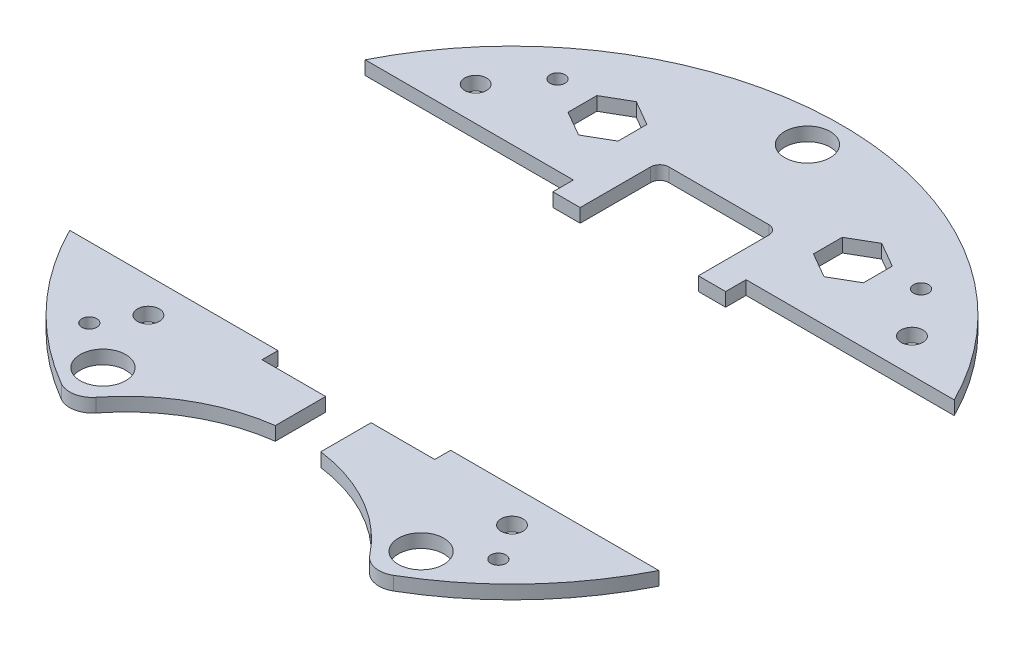
SolidWorks part; units mm, degrees
material "Acrylic (Medium-high impact)"
ref_plane "Front Plane" through (0, 0, 0) normal (0, 0, 1) x (1, 0, 0)
ref_plane "Top Plane" through (0, 0, 0) normal (0, 1, 0) x (1, 0, 0)
ref_plane "Right Plane" through (0, 0, 0) normal (1, 0, 0) x (0, 0, -1)
sketch "Sketch1" plane through (0, 0, 0) normal (0, 1, 0) x (1, 0, 0)
  line L0 (0, -85) -> (-32.4891, -64.8129) construction
  line L1 (0, -85) -> (0, 0) construction
  arc A0 (36.5434, -62.6165) -> (-36.5434, -62.6165) centre (0, 0) ccw
  arc A1 (30.0898, -61.3851) -> (-30.0898, -61.3851) centre (0, -85) ccw
  arc A2 (36.5434, -62.6165) -> (30.0898, -61.3851) centre (34.0231, -58.2982) cw
  arc A3 (-30.0898, -61.3851) -> (-36.5434, -62.6165) centre (-34.0231, -58.2982) cw
  dimension "D1" = 145
  dimension "D2" = 76.5
  dimension "D4" = 5
  dimension "D3" = 85
extrude "Boss-Extrude1" add sketch "Sketch1" along normal blind 3
sketch "solenoid placement" plane through (0, 3, 0) normal (0, 1, 0) x (1, 0, 0)
  line L4 (-19, -36) -> (19, -36)
  line L5 (-19, 28) -> (-19, -36)
  line L6 (19, 28) -> (-19, 28)
  line L7 (19, -36) -> (19, 28)
  line L8 (-19, -36) -> (19, -36)
  line L9 (-19, 28) -> (-19, -36)
  line L10 (19, 28) -> (-19, 28)
  line L11 (19, -36) -> (19, 28)
  dimension "D1" = 0
extrude "Cut-Extrude1" cut sketch "solenoid placement" against normal through all
sketch "Sketch4" plane through (0, 3, 0) normal (0, 1, 0) x (1, 0, 0)
  line L6 (19, 28) -> (-19, 28) construction
  line L10 (-13, 28) -> (13, 28)
  line L11 (13, 28) -> (13, 43.5)
  line L12 (11, 45.5) -> (-11, 45.5)
  line L13 (-13, 43.5) -> (-13, 28)
  arc A5 (13, 43.5) -> (11, 45.5) centre (11, 43.5) ccw
  arc A7 (-11, 45.5) -> (-13, 43.5) centre (-11, 43.5) ccw
  point P10 (0, 28)
  point P11 (0, 28)
  dimension "D3" = 2
  dimension "D1" = 26
  dimension "D2" = 17.5
extrude "Cut-Extrude4" cut sketch "Sketch4" against normal through all
sketch "Sketch5" plane through (0, 3, 0) normal (0, 1, 0) x (1, 0, 0)
  line L6 (0, 0) -> (0, 72.5) construction
  line L7 (-21.5, 51.1754) -> (-27, 54.3509)
  line L8 (-27, 54.3509) -> (-32.5, 51.1754)
  line L9 (-32.5, 51.1754) -> (-32.5, 44.8246)
  line L10 (-32.5, 44.8246) -> (-27, 41.6491)
  line L11 (-27, 41.6491) -> (-21.5, 44.8246)
  line L12 (-21.5, 44.8246) -> (-21.5, 51.1754)
  line L13 (21.5, 44.8246) -> (21.5, 51.1754)
  line L14 (27, 41.6491) -> (21.5, 44.8246)
  line L15 (32.5, 44.8246) -> (27, 41.6491)
  line L16 (32.5, 51.1754) -> (32.5, 44.8246)
  line L17 (27, 54.3509) -> (32.5, 51.1754)
  line L18 (21.5, 51.1754) -> (27, 54.3509)
  circle A0 centre (-27, 48) radius 5.5 construction
  arc A1 (36.5434, -62.6165) -> (-36.5434, -62.6165) centre (0, 0) ccw construction
  circle A2 centre (27, 48) radius 5.5 construction
  dimension "D1" = 11
extrude "Cut-Extrude5" cut sketch "Sketch5" against normal through all
sketch "Sketch6" plane through (0, 3, 0) normal (0, 1, 0) x (1, 0, 0)
  circle A1 centre (40, -40) radius 2.4
  circle A2 centre (40, -40) radius 2.4
  circle A3 centre (-40, -40) radius 2.4
  circle A4 centre (-40, -40) radius 2.4
  circle A5 centre (48, 40) radius 2.4
  circle A6 centre (48, 40) radius 2.4
  circle A7 centre (-48, 40) radius 2.4
  circle A8 centre (-48, 40) radius 2.4
  dimension "D1" = 0
  dimension "D2" = 0
  dimension "D3" = 0
  dimension "D4" = 0
extrude "Cut-Extrude6" cut sketch "Sketch6" against normal through all
sketch "Sketch3" plane through (0, 3, 0) normal (0, 1, 0) x (1, 0, 0)
  line L0 (-19, 28) -> (-19, 32.5)
  line L1 (72.5, -32.5) -> (-72.5, -32.5)
  line L2 (72.5, -32.5) -> (72.5, 32.5)
  line L3 (72.5, 32.5) -> (19, 32.5)
  line L4 (-72.5, -32.5) -> (-72.5, 32.5)
  line L5 (72.5, -32.5) -> (-72.5, 32.5) construction
  line L6 (72.5, 32.5) -> (-72.5, -32.5) construction
  line L7 (-19, 28) -> (19, 28)
  line L8 (19, 28) -> (19, 32.5)
  line L9 (-19, 32.5) -> (-72.5, 32.5)
  arc A0 (36.5434, -62.6165) -> (-36.5434, -62.6165) centre (0, 0) ccw construction
  point P0 (0, 0)
  dimension "D1" = 65
extrude "Cut-Extrude3" cut sketch "Sketch3" against normal through all
sketch "Sketch7" plane through (0, 3, 0) normal (0, 1, 0) x (1, 0, 0)
  line L5 (-5, 0) -> (5, 0)
  line L6 (-5, 0) -> (-5, -50)
  line L7 (-5, -50) -> (5, -50)
  line L8 (5, 0) -> (5, -50)
  point P4 (0, 0)
  dimension "D1" = 10
  dimension "D2" = 50
extrude "Cut-Extrude7" cut sketch "Sketch7" against normal through all
sketch "Sketch9" plane through (0, 3, 0) normal (0, -1, 0) x (1, 0, 0)
  circle A1 centre (35, 55) radius 5
  circle A2 centre (35, 55) radius 5
  circle A3 centre (-35, 55) radius 5
  circle A4 centre (-35, 55) radius 5
  dimension "D1" = 0
  dimension "D2" = 0
extrude "Cut-Extrude11" cut sketch "Sketch9" along normal through all
sketch "Sketch10" plane through (0, 3, 0) normal (0, 1, 0) x (1, 0, 0)
  circle A1 centre (0, 65) radius 5
  circle A2 centre (0, 65) radius 5
  dimension "D1" = 0
extrude "Cut-Extrude12" cut sketch "Sketch10" against normal through all and the other way through all
sketch "Sketch11" plane through (0, 3, 0) normal (0, 1, 0) x (1, 0, 0)
  line L0 (0, 0) -> (0, -22.1714) construction
  circle A0 centre (45, -48) radius 1.65
  circle A1 centre (-45, -48) radius 1.65
  circle A2 centre (40, 50) radius 1.65
  circle A4 centre (-40, 50) radius 1.65
  point P9 (0, 0)
  point P11 (67.1523, 71.4895)
  point P15 (-1.2909, 2.0156)
  dimension "D3" = 3.3
  dimension "D1" = 45
  dimension "D2" = 48
  dimension "D4" = 40
  dimension "D5" = 50
extrude "Cut-Extrude13" cut sketch "Sketch11" against normal through all
equation "\"smallPulleyTeeth\"= 30"
equation "\"largePulleyTeeth\"= 30"
equation "\"eighthThick\"= 3.0mm"
equation "\"sixteenthThick\" = 1.7mm"
equation "\"quarterThick\"=6.0mm"
equation "\"OD\" = 145mm"
equation "\"puckAngle\" = 60.5deg"
equation "\"D1@Sketch1\"=\"OD\""
equation "\"puckDiam\" = 76.5mm"
equation "\"D2@Sketch1\"=\"puckDiam\""
equation "\"D1@Boss-Extrude1\"=\"eighthThick\""
equation "\"axlePress\" = 5.9mm"
equation "\"press\" = 0.2mm"
equation "\"wheelClear\" = 0.3mm"
equation "\"10-32clear\" = 4.8mm"
equation "\"6-32clear\" = 3.3mm"
equation "\"8-32clear\" = 4.0mm"
equation "\"wheelHeight\" = 22mm"
equation "\"wheelWell\" = 65mm"
equation "\"D1@Sketch3\"=\"wheelWell\""
equation "\"puckDist\" = 85mm"
equation "\"scoopFillet\" = 5mm"
equation "\"4-40clear\" = 3.0mm"
equation "\"D3@Sketch1\"=\"puckDist\""
equation "\"D4@Sketch1\"=\"scoopFillet\""
equation "\"D3@Sketch11\"=\"6-32clear\""
